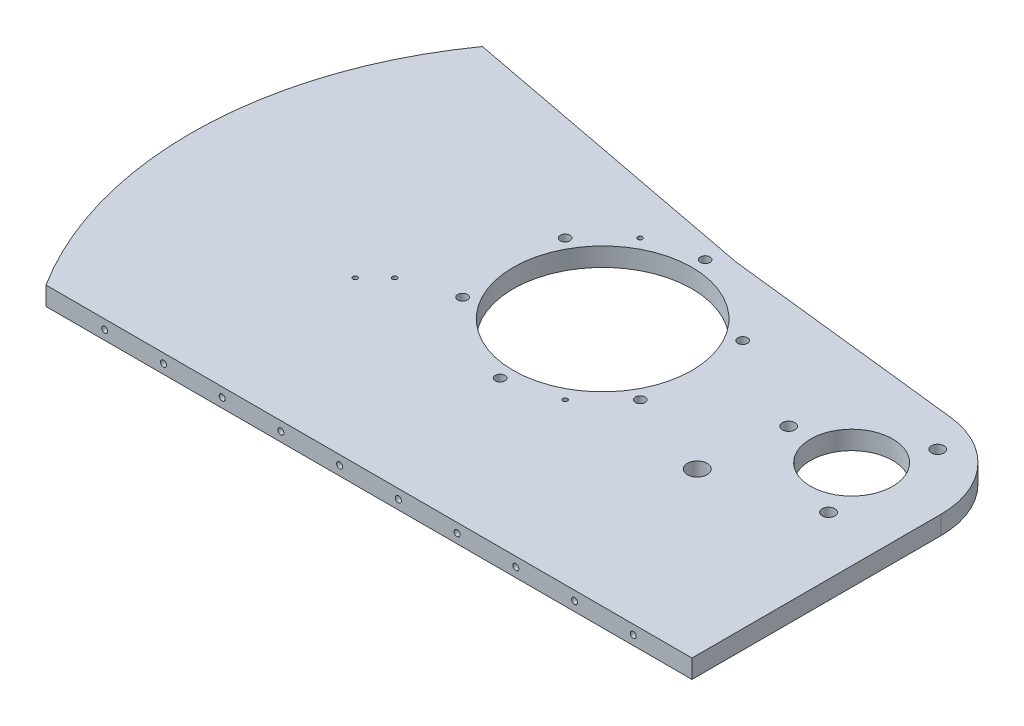
SolidWorks part; units mm, degrees
material "6061 Alloy"
ref_plane "Front Plane" through (0, 0, 0) normal (0, 0, 1) x (1, 0, 0)
ref_plane "Top Plane" through (0, 0, 0) normal (0, 1, 0) x (1, 0, 0)
ref_plane "Right Plane" through (0, 0, 0) normal (1, 0, 0) x (0, 0, -1)
sketch "Sketch1" plane through (0, 0, 0) normal (0, 1, 0) x (1, 0, 0)
  line L0 (4.4706, 39.7494) -> (88.4088, 30.3089)
  line L1 (-40, 40) -> (115.5, 40)
  line L2 (-40, 40) -> (-40, -85)
  line L3 (-40, -85) -> (115.5, -85)
  line L4 (115.5, 40) -> (115.5, -85)
  line L5 (-40, 40) -> (115.5, -85) construction
  line L6 (-40, -85) -> (115.5, 40) construction
  line L7 (-101.026, 60) -> (7.4977, 39.291)
  line L8 (-40, -85) -> (-105, -85)
  circle A0 centre (0, 0) radius 40
  circle A1 centre (0, 0) radius 30.5
  circle A2 centre (85, 0) radius 14
  circle A3 centre (85, 0) radius 30.5
  circle A5 centre (0, 0) radius 117.5 construction
  arc A6 (-101.026, 60) -> (-105, -85) centre (4.8344, -15.4558) ccw
  point P4 (37.75, -22.5)
  dimension "D3" = 80
  dimension "D4" = 61
  dimension "D5" = 61
  dimension "D6" = 28
  dimension "D2" = 235
  dimension "D8" = 130
  dimension "D1" = 85
  dimension "D7" = 85
  dimension "D9" = 65
  dimension "D10" = 20
extrude "Boss-Extrude1" add sketch "Sketch1" along normal mid plane 6.35 contours A0 L0 L1 | A0 L0 | A3 L0 A0 L2 L3 L4 | A0 A1 | A0 L1 L2 | L2 L1 | A3 A2 region at (3.6102, 0, -39.8797) region at (5.9894, 0, -39.555) region at (5.8191, 0, -38.4306) region at (41.203, 0, 46.4586) region at (-31.0653, 0, -31.0653) region at (-79.0131, 0, 14.358) region at (107.0969, 0, -19.751)
hole_wizard "M4x0.7 Tapped Hole1" positions "Sketch4" profile "Sketch5" tap size "M4x0.7" standard "ANSI Metric" end condition up to next
sketch "Sketch4" plane through (0, 3.175, 0) normal (0, 1, 0) x (1, 0, 0)
  line L0 (0, 0) -> (0, 35)
  line L1 (0, 0) -> (30.3109, 17.5)
  line L2 (0, 0) -> (30.3109, -17.5)
  line L3 (0, 0) -> (0, -35)
  line L4 (0, 0) -> (-30.3109, -17.5)
  line L5 (0, 0) -> (-30.3109, 17.5)
  point P5 (0, 35)
  point P16 (30.3109, 17.5)
  point P17 (30.3109, -17.5)
  point P18 (0, -35)
  point P19 (-30.3109, -17.5)
  point P20 (-30.3109, 17.5)
  dimension "D1" = 35
  dimension "D2" = 6
sketch "Sketch5" plane through (-30.3109, 3.175, -17.5) normal (1, 0, 0) x (0, 0, 1)
  line L0 (0, 0) -> (0, 6.35)
  line L1 (0, 6.35) -> (1.65, 6.35)
  line L2 (1.65, 6.35) -> (1.65, 0)
  line L5 (1.65, 0) -> (0, 0)
  line L11 (0, -6.35) -> (0, 107.95) construction
  dimension "Thru Tap Drill Dia." = 3.3
  dimension "Thru Tap Drill Depth" = 6.35
cosmetic thread "Hole Thread1" parameters "D2"=4
cosmetic thread "Hole Thread2" parameters "D2"=4
cosmetic thread "Hole Thread3" parameters "D2"=4
cosmetic thread "Hole Thread4" parameters "D2"=4
cosmetic thread "Hole Thread5" parameters "D2"=4
cosmetic thread "Hole Thread6" parameters "D2"=4
hole_wizard "M4 Clearance Hole1" positions "Sketch6" profile "Sketch7" hole size "M4" standard "ANSI Metric" end condition up to next
sketch "Sketch6" plane through (0, 3.175, 0) normal (0, 1, 0) x (1, 0, 0)
  line L0 (85, 0) -> (95.75, 18.6195)
  line L1 (85, 0) -> (95.75, -18.6195)
  line L2 (85, 0) -> (63.5, 0)
  point P2 (95.75, 18.6195)
  point P10 (95.75, -18.6195)
  point P11 (63.5, 0)
  dimension "D1" = 21.5
  dimension "D2" = 3
sketch "Sketch7" plane through (63.5, 3.175, 0) normal (1, 0, 0) x (0, 0, 1)
  line L0 (0, 0) -> (0, 6.35)
  line L1 (0, 6.35) -> (2.15, 6.35)
  line L2 (2.15, 6.35) -> (2.15, 0)
  line L5 (2.15, 0) -> (0, 0)
  line L11 (0, -6.35) -> (0, 107.95) construction
  dimension "Thru Hole Dia." = 4.3
  dimension "Thru Hole Depth" = 6.35
hole_wizard "M2.5x0.45 Tapped Hole1" positions "Sketch8" profile "Sketch9" tap size "M2.5x0.45" standard "ANSI Metric"
sketch "Sketch8" plane through (0, 0, 85) normal (0, 0, 1) x (1, 0, 0)
  line L0 (-105, 0) -> (-84.9545, 0) construction
  line L1 (-105, 3.175) -> (-105, -3.175) construction
  line L2 (-84.9545, 0) -> (-64.9091, 0) construction
  line L3 (-64.9091, 0) -> (-44.8636, 0) construction
  line L4 (-44.8636, 0) -> (-24.8182, 0) construction
  line L5 (-24.8182, 0) -> (-4.7727, 0) construction
  line L6 (-4.7727, 0) -> (15.2727, 0) construction
  line L7 (15.2727, 0) -> (35.3182, 0) construction
  line L8 (35.3182, 0) -> (55.3636, 0) construction
  line L9 (55.3636, 0) -> (75.4091, 0) construction
  line L10 (75.4091, 0) -> (95.4545, 0) construction
  line L11 (95.4545, 0) -> (115.5, 0) construction
  line L12 (115.5, 3.175) -> (115.5, -3.175) construction
  point P4 (-84.9545, 0)
  point P9 (-64.9091, 0)
  point P11 (-44.8636, 0)
  point P13 (-24.8182, 0)
  point P15 (-4.7727, 0)
  point P17 (15.2727, 0)
  point P19 (35.3182, 0)
  point P21 (55.3636, 0)
  point P23 (75.4091, 0)
  point P25 (95.4545, 0)
sketch "Sketch9" plane through (95.4545, 0, 85) normal (1, 0, 0) x (0, -1, 0)
  line L0 (0, 0) -> (0, 15.6159)
  line L1 (0, 15.6159) -> (1.025, 15)
  line L2 (1.025, 15) -> (1.025, 0)
  line L5 (1.025, 0) -> (0, 0)
  line L10 (0, 15.6159) -> (-1.025, 15) construction
  line L11 (0, -6.35) -> (0, 107.95) construction
  dimension "Tap Drill Dia." = 2.05
  dimension "Tap Drill Depth" = 15
  dimension "Drill Angle" = 118
cosmetic thread "Hole Thread7" parameters "D1"=5, "D2"=2.5
cosmetic thread "Hole Thread8" parameters "D1"=5, "D2"=2.5
cosmetic thread "Hole Thread9" parameters "D1"=5, "D2"=2.5
cosmetic thread "Hole Thread10" parameters "D1"=5, "D2"=2.5
cosmetic thread "Hole Thread11" parameters "D1"=5, "D2"=2.5
cosmetic thread "Hole Thread12" parameters "D1"=5, "D2"=2.5
cosmetic thread "Hole Thread13" parameters "D1"=5, "D2"=2.5
cosmetic thread "Hole Thread14" parameters "D1"=5, "D2"=2.5
cosmetic thread "Hole Thread15" parameters "D1"=5, "D2"=2.5
cosmetic thread "Hole Thread16" parameters "D1"=5, "D2"=2.5
hole_wizard "M2.5x0.45 Tapped Hole2" positions "3DSketch1" profile "Sketch10" tap size "M2.5x0.45" standard "ANSI Metric"
sketch3d "3DSketch1"
  line L0 (-105, 3.175, 85) -> (-105, -3.175, 85) construction
  line L1 (-107.593, -3.175, 80.7249) -> (-107.593, 0, 80.7249)
  arc A0 (-101.026, -3.175, -60) -> (-105, -3.175, 85) centre (4.8344, -3.175, 15.4558) ccw construction
  point P0 (-107.593, 0, 80.7249)
  point P10 (4.8344, 126.825, 15.4558)
  dimension "D1" = 5
  dimension "D2" = 3.175
sketch "Sketch10" plane through (-107.593, 0, 80.7249) normal (0, 1, 0) x (0.5021, 0, 0.8648)
  line L0 (0, 0) -> (0, 15.6159)
  line L1 (0, 15.6159) -> (1.025, 15)
  line L2 (1.025, 15) -> (1.025, 0)
  line L5 (1.025, 0) -> (0, 0)
  line L10 (0, 15.6159) -> (-1.025, 15) construction
  line L11 (0, -6.35) -> (0, 107.95) construction
  dimension "Tap Drill Dia." = 2.05
  dimension "Tap Drill Depth" = 15
  dimension "Drill Angle" = 118
cosmetic thread "Hole Thread17" parameters "D1"=5, "D2"=2.5
pattern_circular "CirPattern1" count 4 over 62.5 about axis through (4.8344, 3.175, 15.4558) along (0, -1, 0) of "M2.5x0.45 Tapped Hole2"
cosmetic thread "Hole Thread18" parameters "D1"=5, "D2"=2.5
cosmetic thread "Hole Thread19" parameters "D1"=5, "D2"=2.5
cosmetic thread "Hole Thread20" parameters "D1"=5, "D2"=2.5
hole_wizard "1/4 Clearance Hole1" positions "Sketch11" profile "Sketch12" hole size "1/4" standard "ANSI Inch" end condition up to next
sketch "Sketch11" plane through (0, 3.175, 0) normal (0, 1, 0) x (1, 0, 0)
  line L0 (60.5414, -28.2309) -> (0, 0)
  line L1 (0, 0) -> (30.5, 0)
  circle A1 centre (60.5414, -28.2309) radius 3.175
  circle A2 centre (0, 0) radius 30.5 construction
  point P0 (60.5414, -28.2309)
  dimension "D1" = 6.35
  dimension "D2" = 66.8
  dimension "D3" = 25
sketch "Sketch12" plane through (60.5414, 3.175, 28.2309) normal (1, 0, 0) x (0, 0, 1)
  line L0 (0, 0) -> (0, 6.35)
  line L1 (0, 6.35) -> (3.3782, 6.35)
  line L2 (3.3782, 6.35) -> (3.3782, 0)
  line L5 (3.3782, 0) -> (0, 0)
  line L11 (0, -6.35) -> (0, 107.95) construction
  dimension "Thru Hole Dia." = 6.7564
  dimension "Thru Hole Depth" = 6.35
hole_wizard "M2x0.4 Tapped Hole1" positions "Sketch13" profile "Sketch14" tap size "M2x0.4" standard "ANSI Metric" end condition up to next
sketch "Sketch13" plane through (0, 3.175, 0) normal (0, 1, 0) x (1, 0, 0)
  line L0 (-54.3468, -30.0803) -> (-47.6293, -23.3628)
  line L2 (0, 0) -> (-60.4323, -60.4323)
  line L4 (0, 0) -> (30.5, 0)
  line L6 (0, 0) -> (-21.5668, 21.5668)
  line L8 (-17.5, 30.3109) -> (17.5, -30.3109)
  circle A0 centre (0, 0) radius 30.5 construction
  point P0 (-47.6293, -23.3628)
  point P2 (-54.3468, -30.0803)
  point P87 (0, 0)
  point P92 (-17.5, 30.3109)
  point P95 (17.5, -30.3109)
  dimension "D1" = 9.5
  dimension "D2" = 135
  dimension "D3" = 17.159
  dimension "D4" = 50.199
  dimension "D5" = 70
  dimension "D6" = 120
sketch "Sketch14" plane through (-47.6293, 3.175, 23.3628) normal (1, 0, 0) x (0, 0, 1)
  line L0 (0, 0) -> (0, 6.35)
  line L1 (0, 6.35) -> (0.8, 6.35)
  line L2 (0.8, 6.35) -> (0.8, 0)
  line L5 (0.8, 0) -> (0, 0)
  line L11 (0, -6.35) -> (0, 107.95) construction
  dimension "Thru Tap Drill Dia." = 1.6
  dimension "Thru Tap Drill Depth" = 6.35
cosmetic thread "Hole Thread21" parameters "D2"=2
cosmetic thread "Hole Thread22" parameters "D2"=2
cosmetic thread "Hole Thread23" parameters "D2"=2
cosmetic thread "Hole Thread24" parameters "D2"=2
